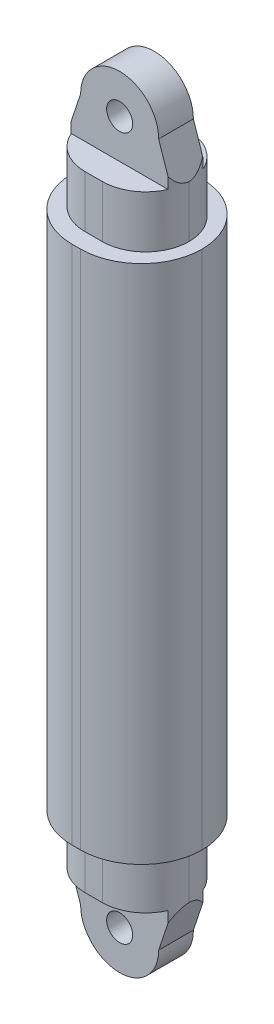
SolidWorks part; units mm, degrees
ref_plane "Front Plane" through (0, 0, 0) normal (0, 0, 1) x (1, 0, 0)
ref_plane "Top Plane" through (0, 0, 0) normal (0, 1, 0) x (1, 0, 0)
ref_plane "Right Plane" through (0, 0, 0) normal (1, 0, 0) x (0, 0, -1)
sketch "Sketch2" plane through (0, 0, 0) normal (0, 0, 1) x (1, 0, 0)
  line L1 (-6, -45) -> (6, -45)
  line L2 (-6, -45) -> (-6, 45)
  line L3 (-6, 45) -> (6, 45)
  line L4 (6, -45) -> (6, 45)
  line L5 (-6, -45) -> (6, 45) construction
  line L6 (-6, 45) -> (6, -45) construction
  point P0 (0, 0)
  dimension "D1" = 90
extrude "Boss-Extrude1" add sketch "Sketch2" along normal blind 10
fillet "Fillet1" radius 5 4 edges at (-6, 0, 0) (6, 0, 0) (6, 0, 10) (-6, 0, 10)
sketch "Sketch3" plane through (0, 0, 0) normal (0, 0, 1) x (1, 0, 0)
  line L0 (-6, -45) -> (-6, 45) construction
  line L1 (6, -45) -> (-6, -45)
  line L2 (6, -45) -> (6, -36)
  line L3 (6, -36) -> (-6, -36)
  line L4 (-6, -45) -> (-6, -36)
  line L6 (-6, -36) -> (-4.5, -40.5)
  line L7 (6, -36) -> (4.5, -40.5)
  arc A0 (-4.5, -40.5) -> (4.5, -40.5) centre (0, -40.5) ccw
  dimension "D1" = 4.5
  dimension "D2" = 9
extrude "Cut-Extrude1" cut sketch "Sketch3" along normal blind 3 contours L6 A0 L7 L3 | A0 L1 L2 L7 | A0 L6 L4 L1 region at (4.7812, -42.2492, 0) region at (-4.7812, -42.2492, 0) region at (0, -39.8597, 0)
extrude "Cut-Extrude2" cut sketch "Sketch3<2>" along normal blind 3 from offset 7 contours L2 L3 L4 L1
sketch "Sketch3<2>" plane through (0, 0, 0) normal (0, 0, 1) x (1, 0, 0) same geometry as "Sketch3"
mirror "Mirror1" about plane through (0, 0, 0) normal (0, 1, 0) of "Cut-Extrude2", "Cut-Extrude1"
extrude "Cut-Extrude4" cut sketch "Sketch3<4>" against normal blind 4 and the other way through all contours A0 L1 L2 L7 | A0 L6 L4 L1 region at (4.7812, -42.2492, 0) region at (-4.7812, -42.2492, 0)
sketch "Sketch3<4>" plane through (0, 0, 0) normal (0, 0, 1) x (1, 0, 0) same geometry as "Sketch3"
sketch "Sketch7" plane through (0, 0, 3) normal (0, 0, -1) x (-1, 0, 0)
  circle A0 centre (0, -40.5) radius 1.5
  dimension "D1" = 3
extrude "Cut-Extrude5" cut sketch "Sketch7" against normal through all
mirror "Mirror3" about plane through (0, 0, 0) normal (0, 1, 0) of "Cut-Extrude5"
mirror "Mirror4" about plane through (0, 0, 0) normal (0, 1, 0) of "Cut-Extrude4"
ref_plane "Plane1" through (0, 0, 5) normal (0, 0, 1) x (1, 0, 0)
sketch "Sketch9" plane through (0, 0, 5) normal (0, 0, 1) x (1, 0, 0)
  line L0 (-7.5, -30) -> (7.5, -30)
  line L1 (-7.5, -30) -> (-7.5, 30)
  line L2 (-7.5, 30) -> (7.5, 30)
  line L3 (7.5, -30) -> (7.5, 30)
  line L4 (-7.5, -30) -> (7.5, 30) construction
  line L5 (-7.5, 30) -> (7.5, -30) construction
  line L6 (0, 30) -> (0, -30) construction
  point P0 (0, 0)
  dimension "D1" = 60
  dimension "D2" = 15
extrude "Boss-Extrude2" add sketch "Sketch9" along normal blind 7 and the other way blind 7
fillet "Fillet3" radius 7 4 edges at (-7.5, 0, 12) (7.5, 0, 12) (7.5, 0, -2) (-7.5, 0, -2)
